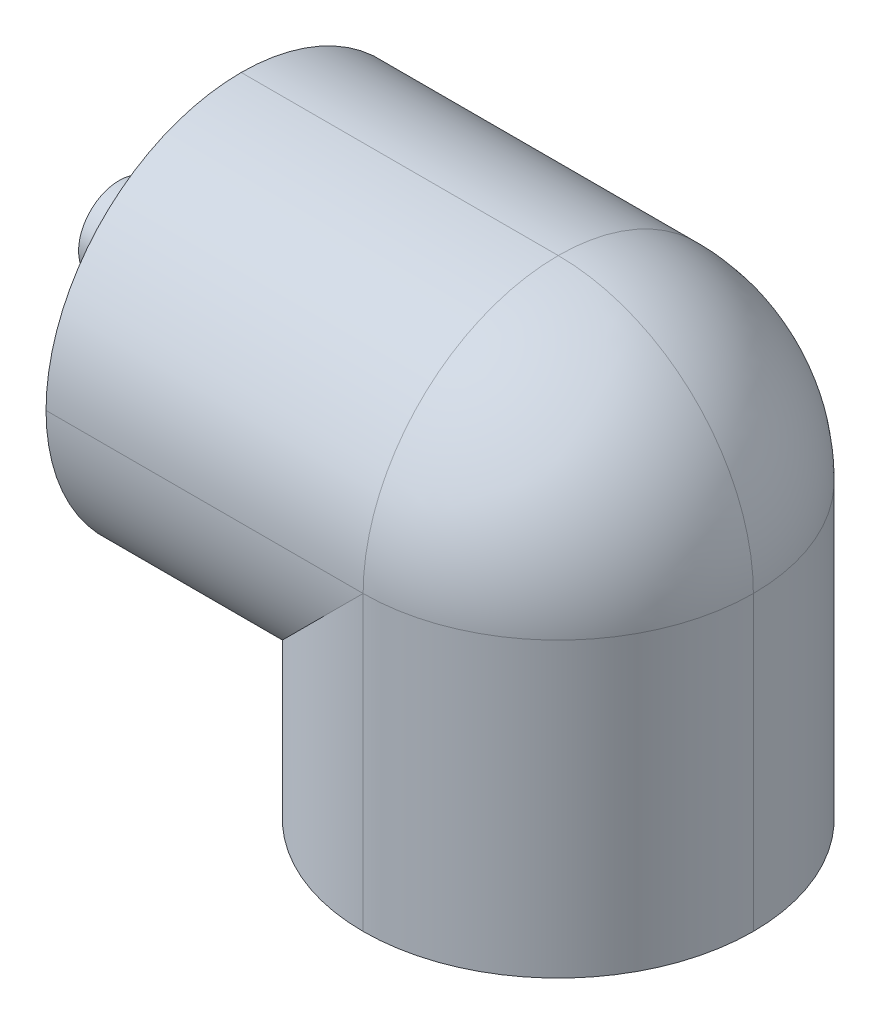
SolidWorks part; units mm, degrees
ref_plane "Front Plane" through (0, 0, 0) normal (0, 0, 1) x (1, 0, 0)
ref_plane "Top Plane" through (0, 0, 0) normal (0, 1, 0) x (1, 0, 0)
ref_plane "Right Plane" through (0, 0, 0) normal (1, 0, 0) x (0, 0, -1)
sketch "Sketch1" plane through (0, 0, 0) normal (0, 1, 0) x (1, 0, 0)
  line L1 (0, 0) -> (48, 0)
  line L2 (0, 0) -> (0, 48)
  line L3 (0, 48) -> (48, 48)
  line L4 (48, 0) -> (48, 48)
  dimension "D1" = 48
  dimension "D2" = 48
extrude "Boss-Extrude1" add sketch "Sketch1" along normal mid plane 60
sketch "Sketch3" plane through (0, 0, 0) normal (-1, 0, 0) x (0, 0, 1)
  line L0 (0, 30) -> (0, -30) construction
  line L1 (-48, 30) -> (0, 30)
  line L2 (-48, 30) -> (-48, -18)
  line L3 (-48, -18) -> (0, -18)
  line L4 (0, 30) -> (0, -18)
  dimension "D1" = 48
extrude "Boss-Extrude2" add sketch "Sketch3" along normal blind 15
fillet "Fillet1" radius 24 8 edges at (-7.5, -18, 0) (-7.5, -18, -48) (48, 0, -48) (48, 0, 0) (0, -24, 0) (0, -24, -48) (16.5, 30, -48) (16.5, 30, 0)
sketch "Sketch4" plane through (0, -30, 0) normal (0, -1, 0) x (-1, 0, 0)
  circle A0 centre (-24, 24) radius 5
  dimension "D1" = 10
extrude "Cut-Extrude1" cut sketch "Sketch4" against normal blind 15
sketch "Sketch5" plane through (-15, 0, 0) normal (-1, 0, 0) x (0, 0, 1)
  circle A0 centre (-24, 6) radius 5
  dimension "D1" = 10
extrude "Boss-Extrude3" add sketch "Sketch5" along normal blind 15
